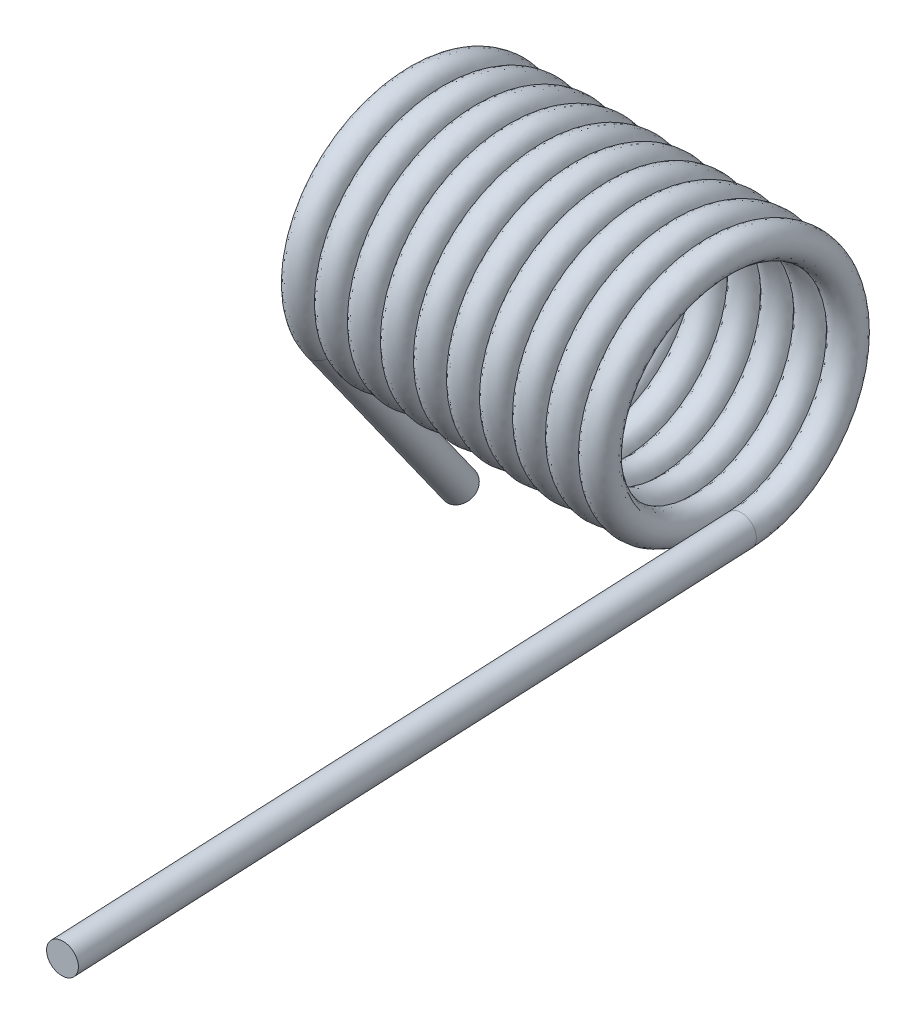
SolidWorks part; units mm, degrees
ref_plane "Front" through (0, 0, 0) normal (0, 0, 1) x (1, 0, 0)
ref_plane "Top" through (0, 0, 0) normal (0, 1, 0) x (1, 0, 0)
ref_plane "Right" through (0, 0, 0) normal (1, 0, 0) x (0, 0, -1)
sketch "Sketch1" plane through (0, 0, 0) normal (1, 0, 0) x (0, 0, -1)
  line L0 (0, -1.0033) -> (0, -1.3081) construction
  line L1 (-1.3081, 0) -> (-1.3081, -9.525) construction
  line L2 (0, -1.3081) -> (-9.525, -1.3081) construction
  line L3 (0, 0) -> (1.3081, 0) construction
  line L4 (0, 0) -> (-1.3081, 0) construction
  line L5 (-9.525, -1.3081) -> (-9.525, -1.0033) construction
  line L6 (-9.525, -1.0033) -> (0, -1.0033) construction
  line L7 (-1.3081, -9.525) -> (-1.0033, -9.525) construction
  line L8 (-1.0033, -9.525) -> (-1.0033, 0) construction
  circle A0 centre (0, 0) radius 1.3081 construction
  circle A1 centre (0, 0) radius 0.762 construction
  circle A2 centre (0, 0) radius 1.1557 construction
  point P7 (0, -1.1557)
  point P10 (0, 1.3081)
  dimension "OD" = 2.6162
  dimension "For Shaft Diameter" = 1.524
  dimension "Wire Diameter" = 0.3048
  dimension "Leg Length" = 9.525
  dimension "Deflection Angle" = 270
sketch "Sketch2" plane through (0, 0, 0) normal (1, 0, 0) x (0, 0, -1)
  circle A0 centre (0, 0) radius 1.1557 construction
  circle A2 centre (0, 0) radius 1.1557
curve "Helix/Spiral1" pitch 0.3302 height 3.2525 radius 1.1557 left hand yes centre (0, 0, 0) axis (-1, 0, 0) start towards (0, 0, -1)
ref_plane "Plane1" through (0, -1.1557, 0) normal (-0.0454, 0, -0.999) x (0.9987, -0.0232, -0.0454)
sketch "Sketch3" plane through (0, -1.1557, 0) normal (-0.0454, 0, -0.999) x (0.9987, -0.0232, -0.0454)
  circle A0 centre (0, 0) radius 0.1524
  dimension "D1" = 0.3048
sweep "Sweep1" add profiles "Sketch3" path "Helix/Spiral1"
sketch "Sketch4" plane through (0, 0, 0) normal (0.0454, 0, 0.999) x (-0.9987, 0.0232, 0.0454)
  circle A1 centre (-0.0269, 1.1554) radius 0.1524
  circle A2 centre (-0.0269, 1.1554) radius 0.1524
  dimension "D1" = 0
extrude "Extrude1" add sketch "Sketch4" along normal blind 7.112
sketch "Sketch5" plane through (-0.0067, -0.1194, -0.0868) normal (-0.0454, -0.8082, -0.5872) x (0.9528, 0.1416, -0.2687)
  circle A1 centre (-3.4462, 0.1255) radius 0.1524
  circle A2 centre (-3.4462, 0.1255) radius 0.1524
  dimension "D1" = 0
extrude "Extrude2" add sketch "Sketch5" along normal blind 2.54
sketch "Sketch6" plane through (0, 0, 0) normal (1, 0, 0) x (0, 0, -1)
  circle A2 centre (0, 0) radius 1.0033 construction
equation "\"D4@Helix/Spiral1\" = \"Wire Diameter@Sketch1\" + .001"
equation "\"D1@Sketch3\"=\"Wire Diameter@Sketch1\""
